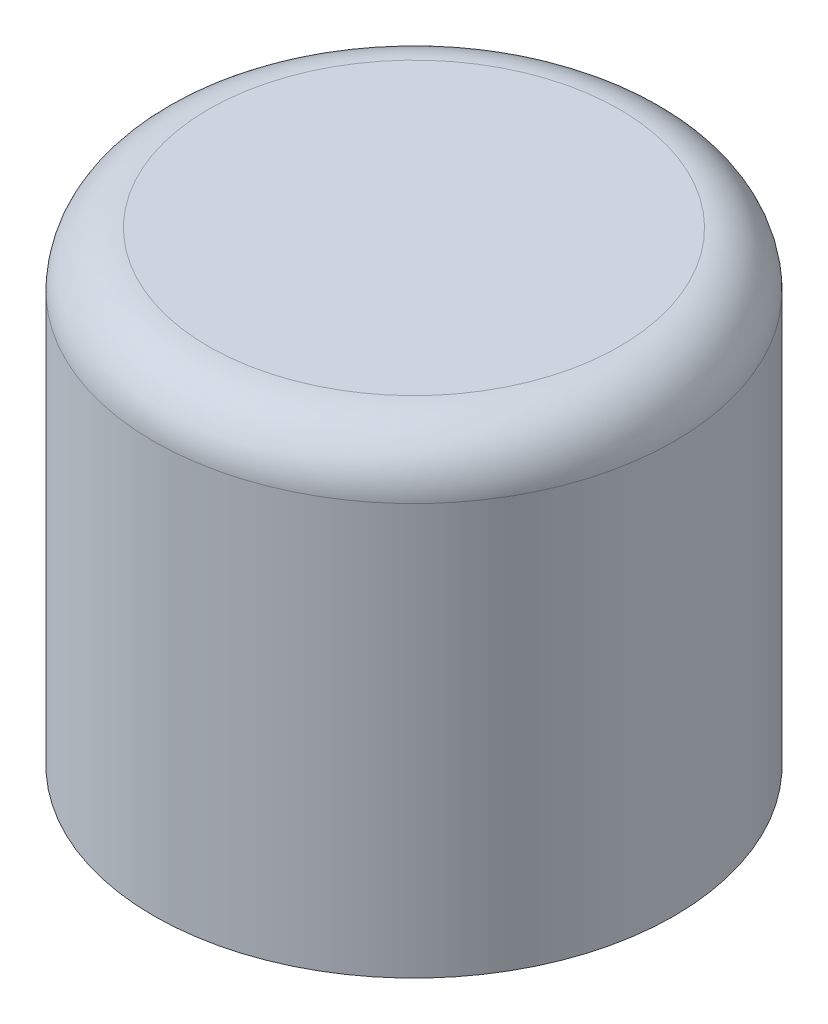
SolidWorks part; units mm, degrees
material "Brass"
ref_plane "Front Plane" through (0, 0, 0) normal (0, 0, 1) x (1, 0, 0)
ref_plane "Top Plane" through (0, 0, 0) normal (0, 1, 0) x (1, 0, 0)
ref_plane "Right Plane" through (0, 0, 0) normal (1, 0, 0) x (0, 0, -1)
sketch "Sketch1" plane through (0, 0, 0) normal (0, 0, 1) x (1, 0, 0)
  line L0 (0, 8.5) -> (0, -8.5) construction
  line L1 (0, 8.5) -> (7.5, 8.5)
  line L2 (9.5, 6.5) -> (9.5, -8.5)
  line L3 (9.5, -8.5) -> (8.5, -8.5)
  line L4 (8.5, -8.5) -> (8.5, -3.5)
  line L7 (5.5, -0.5) -> (0, -0.5)
  line L8 (0, -0.5) -> (0, 8.5)
  line L12 (8.5, -3.5) -> (5.5, -0.5)
  arc A0 (7.5, 8.5) -> (9.5, 6.5) centre (7.5, 6.5) cw
  point P3 (0, 0)
  point P8 (7.5, 6.5)
  point P9 (4, 6.5)
  point P10 (4, -0.5)
  point P14 (8.5, -0.5)
  dimension "D7" = 2
  dimension "D1" = 17
  dimension "D2" = 9.5
  dimension "D3" = 1
  dimension "D4" = 9
revolve "Revolve1" add sketch "Sketch1" angle 360 about L0
sketch "Sketch2" plane through (0, -0.5, 0) normal (0, -1, 0) x (1, 0, 0)
  circle A1 centre (0, 0) radius 3.175
  dimension "D1" = 6.35
extrude "Cut-Extrude1" cut sketch "Sketch2" against normal offset from surface (7 mm away) 2 up to face at (-7.5, 8.5, 0)
sketch "Sketch3" plane through (0, 0, 0) normal (0, 0, 1) x (1, 0, 0)
  line L0 (7.5, 8.5) -> (-7.5, 8.5) construction
  circle A0 centre (0, 2.5) radius 1.1303
  dimension "D1" = 2.2606
  dimension "D2" = 6
extrude "Cut-Extrude2" cut sketch "Sketch3" against normal up to surface (9.4325 mm away) up to face at (-9.5, 6.5, 0)
